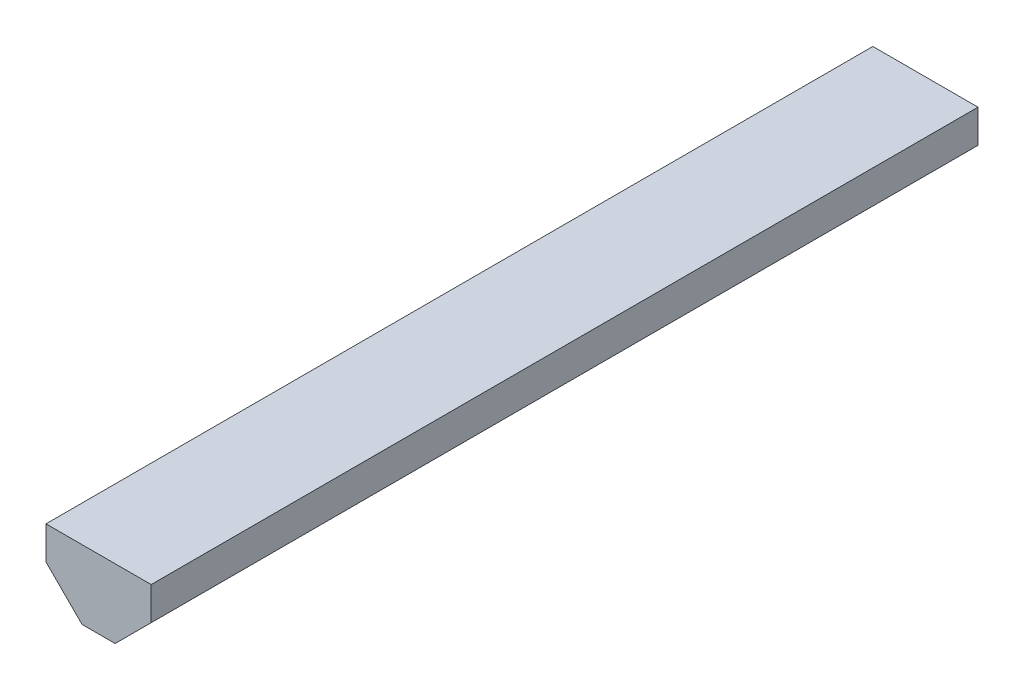
SolidWorks part; units mm, degrees
ref_plane "Front Plane" through (0, 0, 0) normal (0, 0, 1) x (1, 0, 0)
ref_plane "Top Plane" through (0, 0, 0) normal (0, 1, 0) x (1, 0, 0)
ref_plane "Right Plane" through (0, 0, 0) normal (1, 0, 0) x (0, 0, -1)
sketch "vtail" plane through (0, 0, 0) normal (0, 0, 1) x (1, 0, 0)
  line L0 (19.05, -60.5751) -> (-19.05, -60.5751)
  line L1 (-19.05, -60.5751) -> (-60.5751, -19.05)
  line L2 (19.05, -60.5751) -> (60.5751, -19.05)
  line L3 (-60.5751, -19.05) -> (-60.5751, 19.05)
  line L4 (-60.5751, 19.05) -> (60.5751, 19.05)
  line L5 (60.5751, 19.05) -> (60.5751, -19.05)
  circle A0 centre (0, 0) radius 63.5 construction
  dimension "D1" = 127
  dimension "D2" = 45
  dimension "D3" = 45
  dimension "D4" = 38.1
extrude "vtail_extrude" add sketch "vtail" along normal blind 952.5
sketch "Sketch3" plane through (39.8126, -39.8126, 0) normal (0.7071, -0.7071, 0) x (0, 0, -1)
  line L0 (-952.5, 0) -> (-901.7, 0) construction
  line L1 (-952.5, -29.3627) -> (-952.5, 29.3627) construction
  circle A0 centre (-901.7, 0) radius 25.9623
  dimension "D2" = 51.9246
  dimension "D1" = 50.8
extrude "Cut-Extrude1" cut sketch "Sketch3" against normal blind 2.54
sketch "Sketch4" plane through (-39.8126, -39.8126, 0) normal (-0.7071, -0.7071, 0) x (0, 0, 1)
  line L0 (952.5, 0) -> (901.7, 0) construction
  line L1 (952.5, 29.3627) -> (952.5, -29.3627) construction
  circle A0 centre (901.7, 0) radius 25.9623
  dimension "D2" = 51.9246
  dimension "D1" = 50.8
extrude "Cut-Extrude2" cut sketch "Sketch4" against normal blind 2.54
equation "\"fuse_diam\"= 10"
equation "\"fuse_rad\"= 5.0"
equation "\"fuse_length\"= 25"
equation "\"wing_rotation_hor\"= 6.25"
equation "\"wing_rotation_vert\"= 3.0"
equation "\"tail_length\"= 37.5"
equation "\"tail_diam\"= 5.0"
equation "\"tail_rad\"= 2.5"
equation "\"tail_connector\"= 12.375"
equation "\"wingspan\"= 100"
equation "\"wing_mount_diam\"= 3"
equation "\"tail_elevation\"= 1.0"
equation "\"tail_chord_length\"= 2.0442750478820733"
equation "\"nose_cone_length\"= 12.5"
equation "\"nose_cone_splinex\"= 9.5"
equation "\"nose_cone_spliney\"= 2.4"
equation "\"wing_chord_length\"= 5"
equation "\"tri_length\"= 1.5"
equation "\"tri_degrees\"= 45"
equation "\"tail_connect_top\"= 2.25"
equation "\"tail_connect_bottom\"= 2.384848003542364"
equation "\"D1@vtail\" = \"tail_diam\""
equation "\"D2@vtail\" = \"tri_degrees\""
equation "\"D3@vtail\" = \"tri_degrees\""
equation "\"D4@vtail\" = \"tri_length\""
equation "\"D1@vtail_extrude\" = \"tail_length\""
equation "\"tail_offset\"= 2"
equation "\"vtail_length\"= 33.5"
equation "\"fillet_rad\"= 0.1"
equation "\"D1@Sketch3\"=\"tail_offset\""
equation "\"D2@Sketch3\"=\"tail_chord_length\""
equation "\"D2@Sketch4\"=\"tail_chord_length\""
